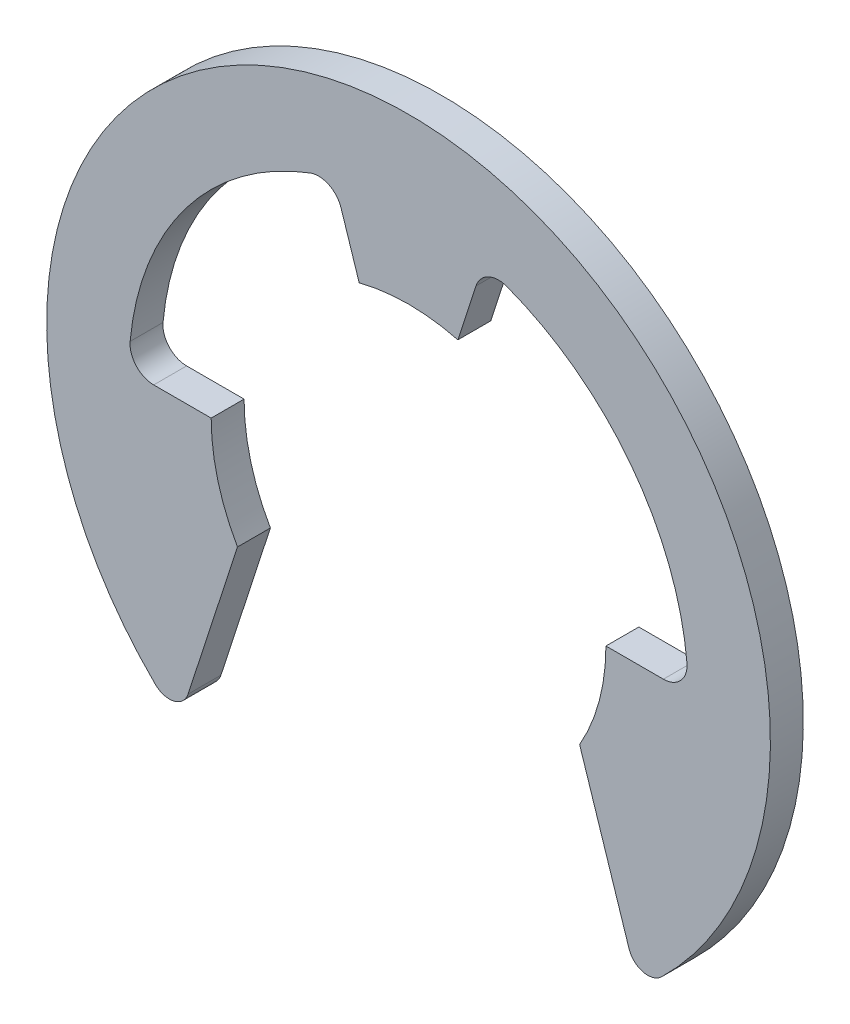
SolidWorks part; units mm, degrees
ref_plane "Front Plane" through (0, 0, 0) normal (0, 0, 1) x (1, 0, 0)
ref_plane "Top Plane" through (0, 0, 0) normal (0, 1, 0) x (1, 0, 0)
ref_plane "Right Plane" through (0, 0, 0) normal (1, 0, 0) x (0, 0, -1)
sketch "BodySke" plane through (0, 0, 0) normal (0, 0, 1) x (1, 0, 0)
  line L0 (-34.7902, 0) -> (37.4871, 0) construction
  line L1 (0, -29.1266) -> (0, 42.3415) construction
  line L2 (10.4, -5.9867) -> (13.4058, -15.2376)
  line L3 (-10.4, -5.9867) -> (-13.4058, -15.2376)
  line L4 (12, 0) -> (17, 0)
  line L5 (-12, 0) -> (-17, 0)
  line L6 (-3, 11.619) -> (-4.5471, 16.3806)
  line L7 (3, 11.619) -> (4.5471, 16.3806)
  arc A0 (15.3863, -15.7245) -> (-15.3863, -15.7245) centre (0, 0) ccw
  arc A1 (-12, 0) -> (-10.4, -5.9867) centre (0, 0) ccw
  arc A2 (-4.5471, 16.3806) -> (-17, 0) centre (0, 0) ccw
  arc A3 (3, 11.619) -> (-3, 11.619) centre (0, 0) ccw
  circle A4 centre (0, 0) radius 17 construction
  circle A5 centre (0, 0) radius 22 construction
  arc A6 (10.4, -5.9867) -> (12, 0) centre (0, 0) ccw
  arc A7 (17, 0) -> (4.5471, 16.3806) centre (0, 0) ccw
  arc A8 (-13.4058, -15.2376) -> (-15.3863, -15.7245) centre (-14.5471, -14.8668) cw
  arc A9 (15.3863, -15.7245) -> (13.4058, -15.2376) centre (14.5471, -14.8668) cw
  point P23 (-13.9755, -16.9908)
  point P26 (13.9755, -16.9908)
  point P29 (-17, 0)
  point P32 (17, 0)
  point P35 (4.5471, 16.3806)
  point P38 (-4.5471, 16.3806)
  dimension "D7" = 6
  dimension "Angle" = 36
extrude "BaseBody" add sketch "BodySke" along normal blind 2
fillet "Fillet1" radius 1.44 4 edges at (17, 0, 1) (4.5471, 16.3806, 1) (-4.5471, 16.3806, 1) (-17, 0, 1)
equation "\"D7@BodySke\" = \"Inside_Diameter@BodySke\" / 4"
equation "\"D8@BodySke\" = \"Inside_Diameter@BodySke\" * 0.05"
equation "\"Fillet_radius@Fillet1\" = \"Inside_Diameter@BodySke\" * 0.06"
